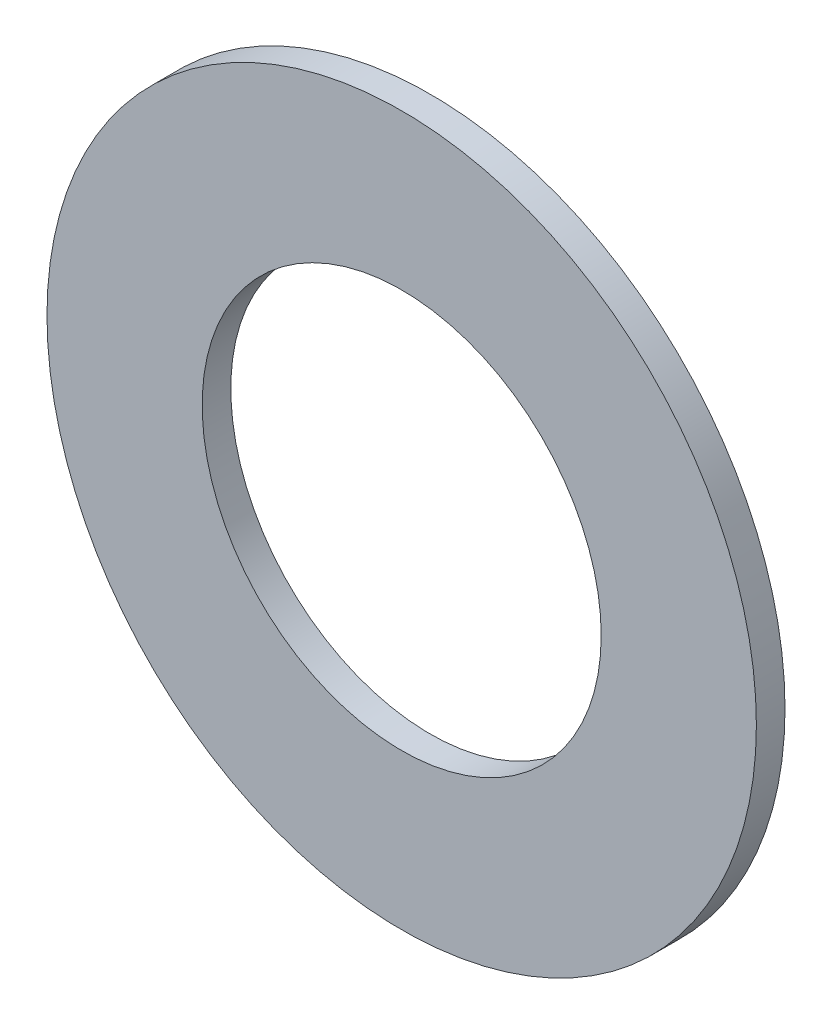
SolidWorks part; units mm, degrees
other "Imported1"
ref_plane "Front Plane" through (0, 0, 0) normal (0, 0, 1) x (1, 0, 0)
ref_plane "Top Plane" through (0, 0, 0) normal (0, 1, 0) x (1, 0, 0)
ref_plane "Right Plane" through (0, 0, 0) normal (1, 0, 0) x (0, 0, -1)
sketch "Sketch1" plane through (0, 0, 0) normal (0, 0, 1) x (1, 0, 0)
  line L0 (-25.4, 0) -> (25.4, 0) construction
  line L1 (-14.2875, 0) -> (14.2875, 0) construction
  circle A0 centre (0, 0) radius 14.2875 construction
  circle A1 centre (0, 0) radius 25.4 construction
  point P8 (0, 0)
  point P9 (0, 25.4)
  point P11 (14.2875, 0)
  dimension "ID" = 28.575
  dimension "OD" = 50.8
sketch "Sketch2" plane through (0, 0, 0) normal (1, 0, 0) x (0, 0, -1)
  line L0 (-1.025, 25.4) -> (1.025, 25.4) construction
  point P2 (0, 25.4)
  dimension "Thickness" = 2.05
sketch "Sketch3" plane through (0, 0, 0) normal (0, 0, 1) x (1, 0, 0)
  circle A0 centre (0, 0) radius 14.2875
  circle A1 centre (0, 0) radius 25.4
extrude "Boss-Extrude1" add sketch "Sketch3" along normal up to vertex (1.025 mm away) and the other way up to vertex (1.025 mm away) up to point (0, 25.4, 1.025) other way up to point (0, 25.4, -1.025)
ref_axis "Center Axis 1" through (0, 0, 1.025) along (0, 0, -1)
